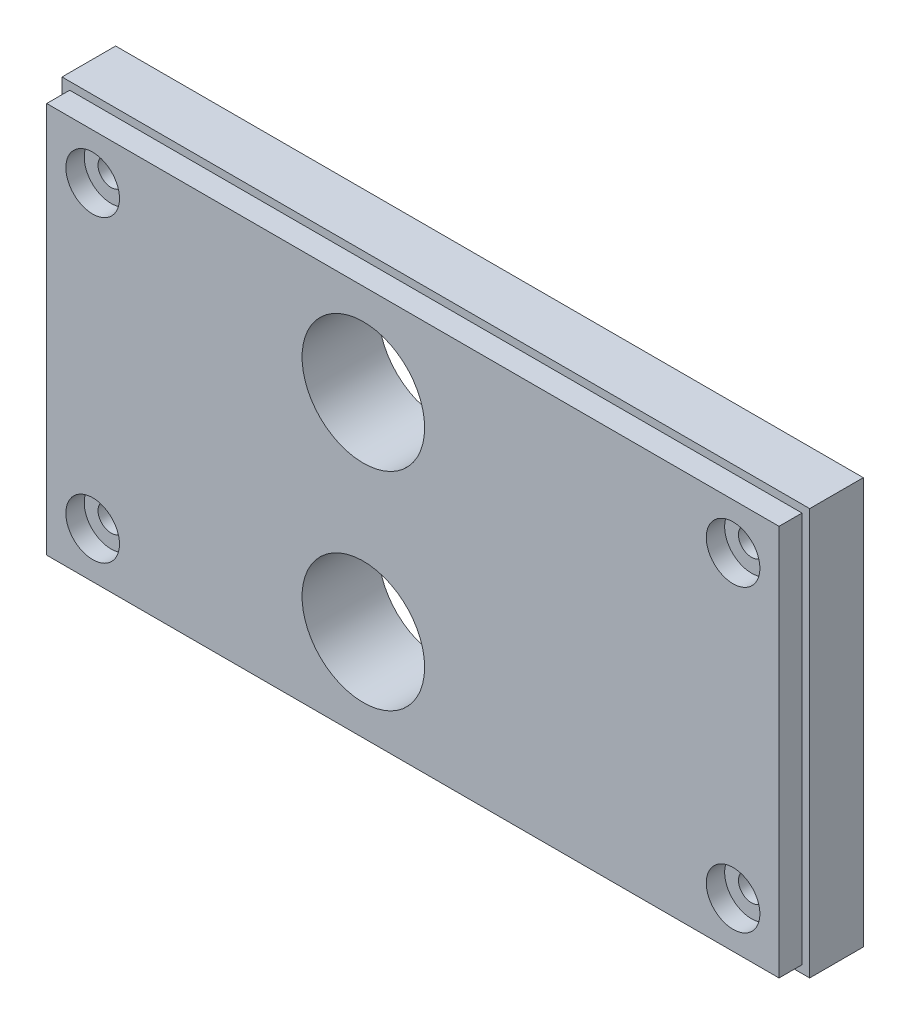
SolidWorks part; units mm, degrees
ref_plane "Płaszczyzna przednia" through (0, 0, 0) normal (0, 0, 1) x (1, 0, 0)
ref_plane "Płaszczyzna górna" through (0, 0, 0) normal (0, 1, 0) x (1, 0, 0)
ref_plane "Płaszczyzna prawa" through (0, 0, 0) normal (1, 0, 0) x (0, 0, -1)
sketch "Szkic1" plane through (0, 0, 0) normal (0, 0, 1) x (1, 0, 0)
  line L1 (130, -76.5359) -> (32.3904, -76.5359)
  line L2 (130, -76.5359) -> (130, -23.4641)
  line L3 (130, -23.4641) -> (32.3904, -23.4641)
  line L4 (32.3904, -76.5359) -> (32.3904, -23.4641)
  line L5 (130, -76.5359) -> (32.3904, -23.4641) construction
  line L6 (130, -23.4641) -> (32.3904, -76.5359) construction
  point P4 (81.1952, -50)
  dimension "D5" = 53.0718
extrude "Dodanie-wyciągnięcie1" add sketch "Szkic1" along normal blind 7
sketch "Szkic2" plane through (0, 0, 7) normal (0, 0, 1) x (1, 0, 0)
  line L0 (130, -23.4641) -> (32.3904, -23.4641) construction
  line L1 (33.3904, -24.4641) -> (129, -24.4641)
  line L2 (33.3904, -24.4641) -> (33.3904, -75.5359)
  line L3 (33.3904, -75.5359) -> (129, -75.5359)
  line L4 (129, -24.4641) -> (129, -75.5359)
  line L5 (33.3904, -24.4641) -> (129, -75.5359) construction
  line L6 (33.3904, -75.5359) -> (129, -24.4641) construction
  line L7 (32.3904, -23.4641) -> (32.3904, -76.5359) construction
  line L8 (32.3904, -76.5359) -> (130, -76.5359) construction
  line L9 (130, -76.5359) -> (130, -23.4641) construction
  point P4 (81.1952, -50)
  dimension "D1" = 1
  dimension "D2" = 1
  dimension "D3" = 1
  dimension "D4" = 1
extrude "Dodanie-wyciągnięcie2" add sketch "Szkic2" along normal blind 3
sketch "Szkic3" plane through (0, 0, 10) normal (0, 0, 1) x (1, 0, 0)
  line L0 (33.3904, -24.4641) -> (33.3904, -75.5359) construction
  line L1 (129, -24.4641) -> (33.3904, -24.4641) construction
  point P0 (39.3904, -30.4641)
  dimension "D1" = 6
  dimension "D2" = 6
hole_wizard "Pogłębienie walcowe pod M3 Śrubę z łbem stożkowym ściętym1" positions "Szkic 3D3" profile "Szkic4" counterbore size "M3" standard "ISO" end condition up to next
sketch3d "Szkic 3D3"
  point P0 (39.3904, -30.4641, 10)
sketch "Szkic4" plane through (39.3904, -30.4641, 10) normal (1, 0, 0) x (0, -1, 0)
  line L0 (0, 0) -> (0, 10.001)
  line L1 (0, 10.001) -> (1.7, 10.001)
  line L3 (1.7, 10.001) -> (1.7, 2.4)
  line L4 (1.7, 2.4) -> (3.5, 2.4)
  line L5 (3.5, 2.4) -> (3.5, 0)
  line L7 (3.5, 0) -> (0, 0)
  line L11 (0, -6.35) -> (0, 107.95) construction
  dimension "Średnica otworu na wylot" = 3.4
  dimension "Głębokość otworu na wylot" = 10.001
  dimension "Średnica pogłębienia walcowego" = 7
  dimension "Głębokość pogłębienia walcowego" = 2.4
ref_plane "Płaszczyzna1" through (0, -76.5359, 0) normal (0, -1, 0) x (-1, 0, 0)
ref_plane "Płaszczyzna2" through (0, -23.4641, 0) normal (0, 1, 0) x (1, 0, 0)
ref_plane "Płaszczyzna3" through (0, -50, 0) normal (0, 1, 0) x (1, 0, 0)
mirror "Lustro1" about plane through (0, -50, 0) normal (0, 1, 0) of "Pogłębienie walcowe pod M3 Śrubę z łbem stożkowym ściętym1"
ref_plane "Płaszczyzna4" through (130, 0, 0) normal (-1, 0, 0) x (0, 0, 1)
ref_plane "Płaszczyzna5" through (81.1952, 0, 0) normal (-1, 0, 0) x (0, 0, 1)
mirror "Lustro2" about plane through (81.1952, 0, 0) normal (-1, 0, 0) of "Lustro1"
sketch "Szkic5" plane through (0, 0, 10) normal (0, 0, 1) x (1, 0, 0)
  line L0 (74.7286, -24.4641) -> (74.7286, -75.5359) construction
  line L1 (129, -24.4641) -> (33.3904, -24.4641) construction
  line L2 (33.3904, -75.5359) -> (129, -75.5359) construction
  circle A0 centre (74.7286, -36.4641) radius 8
  circle A1 centre (74.7286, -63.5359) radius 8
  dimension "D1" = 12
  dimension "D2" = 16
  dimension "D3" = 12
extrude "Wytnij-wyciągnięcie1" cut sketch "Szkic5" against normal up to next
